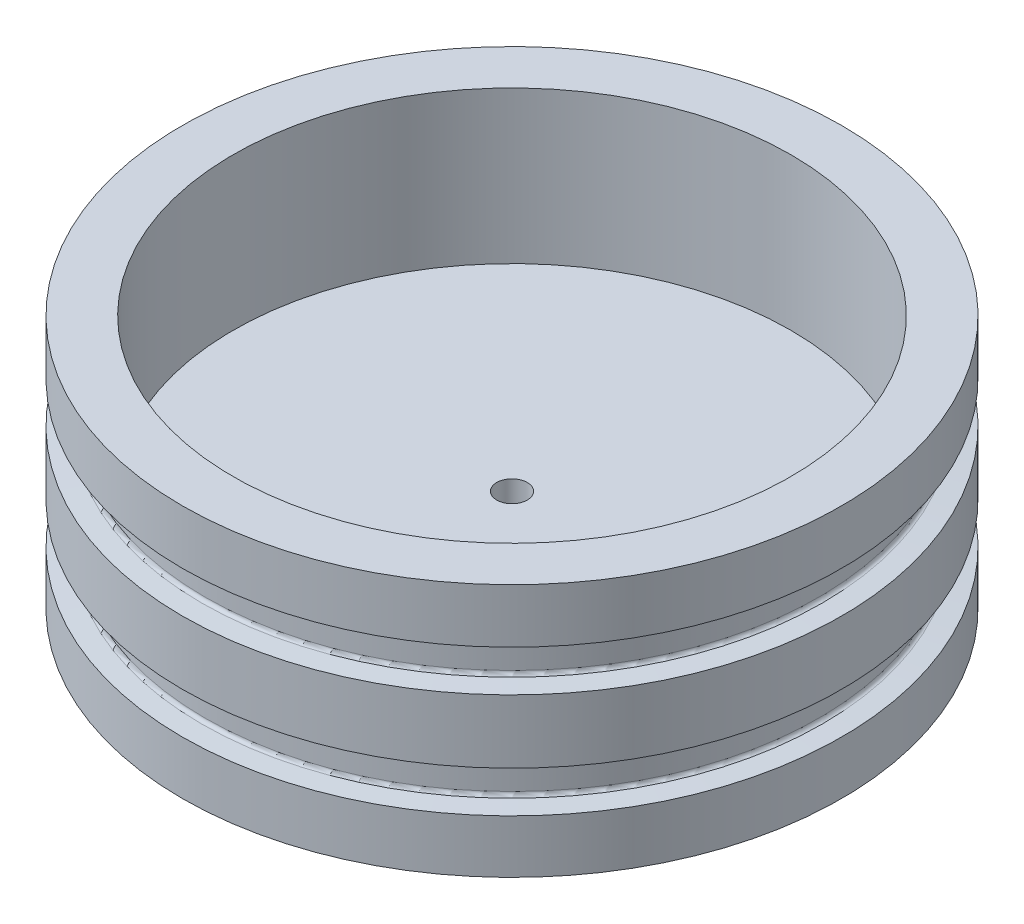
SolidWorks part; units mm, degrees
material "1060 Alloy"
ref_plane "Front Plane" through (0, 0, 0) normal (0, 0, 1) x (1, 0, 0)
ref_plane "Top Plane" through (0, 0, 0) normal (0, 1, 0) x (1, 0, 0)
ref_plane "Right Plane" through (0, 0, 0) normal (1, 0, 0) x (0, 0, -1)
sketch "Sketch1" plane through (0, 0, 0) normal (0, 0, 1) x (1, 0, 0)
  line L0 (0, 0) -> (0, 25.4) construction
  line L1 (-41.275, 11.176) -> (-41.275, 42.926)
  line L2 (-41.275, 11.176) -> (-5.1435, 11.176)
  line L3 (-1.9133, 0) -> (-1.9133, 23.876)
  line L4 (-1.9133, 23.876) -> (-34.925, 23.876)
  line L5 (-34.925, 23.876) -> (-34.925, 42.926)
  line L6 (-34.925, 42.926) -> (-41.275, 42.926)
  line L8 (-1.9133, 0) -> (-5.1435, 0)
  line L9 (-5.1435, 0) -> (-5.1435, 11.176)
  line L11 (55, 0) -> (-55, 0) construction
  dimension "D1" = 1.9133
  dimension "D2" = 34.925
  dimension "D3" = 31.75
  dimension "D4" = 6.35
  dimension "D5" = 12.7
  dimension "D6" = 11.176
  dimension "D7" = 5.1435
revolve "Revolve1" add sketch "Sketch1" angle 360 about L0
ref_plane "Plane1" through (0, 0, 0) normal (-1, 0, 0) x (0, 0, -1)
ref_plane "Plane2" through (0, 0, 0) normal (-1, 0, 0) x (0, 0, -1)
ref_plane "Plane3" through (0, 0, 0) normal (-1, 0, 0) x (0, 0, -1)
ref_plane "Plane4" through (0, 0, 0) normal (-1, 0, 0) x (0, 0, -1)
ref_plane "Plane5" through (0, 0, 0) normal (-1, 0, 0) x (0, 0, -1)
ref_plane "Plane6" through (0, 0, 0) normal (-1, 0, 0) x (0, 0, -1)
ref_plane "Plane7" through (0, 0, 0) normal (-1, 0, 0) x (0, 0, -1)
ref_plane "Plane8" through (0, 0, 0) normal (-1, 0, 0) x (0, 0, -1)
sketch "Sketch3" plane through (0, 0, 0) normal (-1, 0, 0) x (0, 0, -1)
  line L0 (38.8614, -31.1839) -> (41.3639, -30.965)
  line L1 (41.3639, -30.965) -> (41.3639, -36.1527)
  line L2 (41.3639, -36.1527) -> (38.8614, -35.9337)
  line L3 (38.4556, -35.4909) -> (38.4556, -31.6267)
  line L4 (0, 50) -> (0, -50) construction
  line L5 (-41.275, -42.926) -> (41.275, -42.926) construction
  arc A0 (38.8614, -35.9337) -> (38.4556, -35.4909) centre (38.9001, -35.4909) cw
  arc A1 (38.4556, -31.6267) -> (38.8614, -31.1839) centre (38.9001, -31.6267) cw
  dimension "D1" = 6.7733
revolve "Groove for AS 568-234, O-Ring1" cut sketch "Sketch3"
pattern_linear "LPattern1" count 2 spacing 13.1233 along (0, -1, 0) of "Groove for AS 568-234, O-Ring1"
